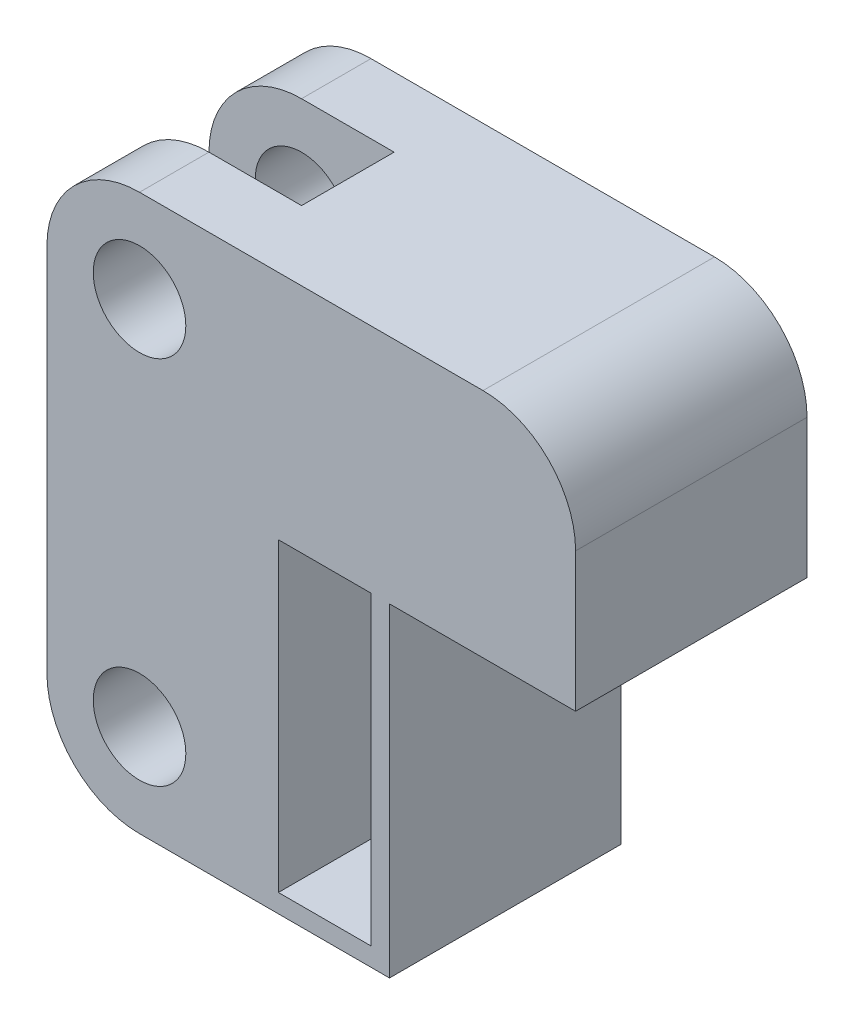
SolidWorks part; units mm, degrees
ref_plane "Front Plane" through (0, 0, 0) normal (0, 0, 1) x (1, 0, 0)
ref_plane "Top Plane" through (0, 0, 0) normal (0, 1, 0) x (1, 0, 0)
ref_plane "Right Plane" through (0, 0, 0) normal (1, 0, 0) x (0, 0, -1)
ref_axis "X" through (-88.99, 0, 0) along (1, 0, 0)
ref_axis "Y" through (0, 55, 0) along (0, -1, 0)
ref_axis "Z" through (0, 0, -88.99) along (0, 0, 1)
sketch "Sketch1" plane through (0, 0, 0) normal (0, 0, 1) x (1, 0, 0)
  line L0 (0, 0) -> (0, -20) construction
  line L1 (0, 0) -> (0, 20) construction
  line L2 (-10, 20) -> (-10, -20)
  line L3 (0, 30) -> (37.1, 30)
  line L4 (47.1, 20) -> (47.1, 5)
  line L5 (47.1, 5) -> (15, 5)
  line L6 (15, 5) -> (15, -30)
  line L7 (15, -30) -> (0, -30)
  line L8 (15, -30) -> (27, -30)
  line L9 (27, -30) -> (27, 5)
  line L10 (25, -28) -> (15, -28)
  line L11 (25, -28) -> (25, 5)
  line L12 (10, -30) -> (10, 30)
  circle A0 centre (0, 20) radius 5
  circle A1 centre (0, -20) radius 5
  arc A2 (-10, -20) -> (0, -30) centre (0, -20) ccw
  arc A3 (-10, 20) -> (0, 30) centre (0, 20) cw
  arc A4 (37.1, 30) -> (47.1, 20) centre (37.1, 20) cw
  dimension "D1" = 20
  dimension "D2" = 10
  dimension "D3" = 5
  dimension "D7" = 15
  dimension "D4" = 20.1
  dimension "D5" = 2
  dimension "D6" = 2
  dimension "D8" = 10
  dimension "D9" = 5
extrude "Boss-Extrude1" add sketch "Sketch1" along normal mid plane 25 contours A4 L3 A3 L2 A2 L7 L6 L5 L4 A1 A0 | A3 L2 A2 L7 L12 L3 A1 A0 | L11 L10 L6 L8 L9 L5 region at (0.3333, 0, 0) region at (25.6279, 12.4398, 0) region at (15.37, -29, 0)
extrude "Cut-Extrude2" cut sketch "Sketch1<3>" against normal mid plane 10 contours A3 L2 A2 L7 L12 L3 A1 A0 region at (0.3333, 0, 0)
sketch "Sketch1<3>" plane through (0, 0, 0) normal (0, 0, 1) x (1, 0, 0) same geometry as "Sketch1"
sketch "Sketch4" plane through (0, 0, 0) normal (0, 1, 0) x (1, 0, 0)
  line L0 (0, 0) -> (20, 0) construction
  line L1 (20, 0) -> (37.05, 0) construction
  line L2 (25, 12.5) -> (15, 12.5) construction
  line L3 (25, 12.5) -> (15, 12.5) construction
  line L4 (20, 12.5) -> (20, 0) construction
  line L5 (47.1, 12.5) -> (27, 12.5) construction
  line L6 (47.1, 12.5) -> (27, 12.5) construction
  line L7 (37.05, 12.5) -> (37.05, 0) construction
  circle A0 centre (20, 0) radius 5
  circle A1 centre (37.05, 0) radius 7.5
  dimension "D1" = 10
  dimension "D2" = 15
extrude "Cut-Extrude3" cut sketch "Sketch4" along normal blind 8 from surface starting at face at (37.05, 5, 0)
